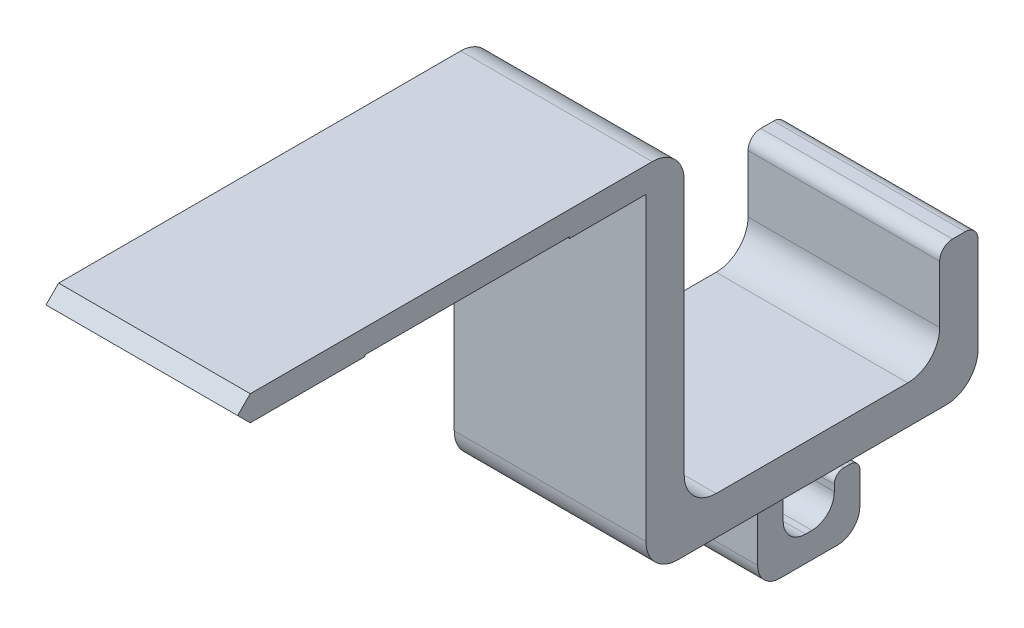
SolidWorks part; units mm, degrees
ref_plane "Front Plane" through (0, 0, 0) normal (0, 0, 1) x (1, 0, 0)
ref_plane "Top Plane" through (0, 0, 0) normal (0, 1, 0) x (1, 0, 0)
ref_plane "Right Plane" through (0, 0, 0) normal (1, 0, 0) x (0, 0, -1)
sketch "Sketch1" plane through (0, 0, 0) normal (1, 0, 0) x (0, 0, -1)
  line L4 (-15, 0) -> (0, 0)
  line L5 (0, 0) -> (0, -50)
  line L6 (0, -50) -> (40, -50)
  line L7 (40, -50) -> (40, -34)
  line L8 (40, -34) -> (46, -34)
  line L9 (46, -34) -> (46, -56)
  line L10 (46, -56) -> (-6, -56)
  line L11 (-6, -56) -> (-6, -3.95)
  line L12 (-6, -3.95) -> (-13.2269, -3.95)
  line L18 (-13.2269, -3.95) -> (-17.9408, -3.95)
  line L19 (-17.9408, -3.95) -> (-17.9408, -3.7)
  line L20 (-17.9408, -3.7) -> (-49.9408, -3.7)
  line L21 (-49.9408, -3.7) -> (-49.9408, -3.95)
  line L22 (-49.9408, -3.95) -> (-69.9408, -3.95)
  line L23 (-69.9408, -3.95) -> (-69.9408, 0)
  line L24 (-69.9408, 0) -> (-15, 0)
  dimension "D5" = 3.95
  dimension "D6" = 6
  dimension "D7" = 6
  dimension "D8" = 6
  dimension "D12" = 22
  dimension "D13" = 50
  dimension "D14" = 40
  dimension "D2" = 3.7
  dimension "D3" = 3.95
  dimension "D4" = 32
  dimension "D9" = 4.7263
  dimension "D10" = 4.7139
  dimension "D11" = 7.2269
  dimension "D15" = 20
extrude "Boss-Extrude1" add sketch "Sketch1" along normal mid plane 30 contours L24 L23 L22 L21 L20 L19 L18 L12 L11 L10 L9 L8 L7 L6 L5 L4 | L10 region at (0, -1.2876, 7.5)
fillet "Fillet2" radius 5 1 edges at (0, 0, 0)
fillet "Fillet3" radius 5 2 edges at (0, -50, -40) (0, -50, 0)
fillet "Fillet4" radius 5 2 edges at (0, -56, -46) (0, -56, 6)
chamfer "Chamfer1" distance 2 angle 45 2 edges at (0, -3.95, 69.9408) (0, 0, 69.9408)
sketch "Sketch3" plane through (0, 0, 0) normal (1, 0, 0) x (0, 0, -1)
  line L0 (19, -56) -> (19, -74)
  line L1 (41, -56) -> (-1, -56) construction
  line L2 (19, -74) -> (35, -74)
  line L3 (35, -74) -> (35, -64)
  line L4 (35, -64) -> (31, -64)
  line L5 (31, -64) -> (31, -70)
  line L6 (31, -70) -> (23, -70)
  line L7 (23, -70) -> (23, -56)
  line L9 (46, -34) -> (46, -51) construction
  line L27 (46, -34) -> (40, -34)
  line L29 (40, -34) -> (40, -45)
  line L30 (35, -50) -> (5, -50)
  line L31 (0, -45) -> (0, -5)
  line L32 (-5, 0) -> (-67.9408, 0)
  line L33 (-67.9408, 0) -> (-69.9158, -1.975)
  line L34 (-69.9158, -1.975) -> (-67.9408, -3.95)
  line L35 (-67.9408, -3.95) -> (-49.9408, -3.95)
  line L36 (-49.9408, -3.95) -> (-49.9408, -3.7)
  line L37 (-49.9408, -3.7) -> (-17.9408, -3.7)
  line L38 (-17.9408, -3.7) -> (-17.9408, -3.95)
  line L39 (-17.9408, -3.95) -> (-6, -3.95)
  line L40 (-6, -3.95) -> (-6, -51)
  line L41 (-1, -56) -> (41, -56)
  line L42 (46, -51) -> (46, -34)
  line L58 (19, -56) -> (23, -56)
  arc A5 (35, -50) -> (40, -45) centre (35, -45) ccw
  arc A6 (0, -45) -> (5, -50) centre (5, -45) ccw
  arc A7 (0, -5) -> (-5, 0) centre (-5, -5) ccw
  arc A8 (-6, -51) -> (-1, -56) centre (-1, -51) ccw
  arc A9 (41, -56) -> (46, -51) centre (41, -51) ccw
  point P9 (33, -64)
  dimension "D1" = 4
  dimension "D2" = 4
  dimension "D4" = 18
  dimension "D5" = 8
  dimension "D6" = 16
  dimension "D7" = 23
extrude "Boss-Extrude2" add sketch "Sketch3" along normal mid plane 15
fillet "Fillet5" radius 3 2 edges at (0, -56, -23) (0, -56, -19)
fillet "Fillet6" radius 3.5 2 edges at (0, -70, -31) (0, -70, -23)
fillet "Fillet7" radius 3.5 2 edges at (0, -74, -35) (0, -74, -19)
fillet "Fillet8" radius 1.5 2 edges at (0, -64, -35) (0, -64, -31)
fillet "Fillet9" radius 2 2 edges at (0, -34, -40) (0, -34, -46)
equation "\"D6@Sketch1\"=6"
equation "\"D7@Sketch1\"=\"D6@Sketch1\""
equation "\"D8@Sketch1\"=\"D6@Sketch1\""
equation "\"D13@Sketch1\"=50"
equation "\"D2@Sketch3\"=\"D1@Sketch3\""
equation "\"D3@Sketch3\"=\"D1@Sketch3\""
